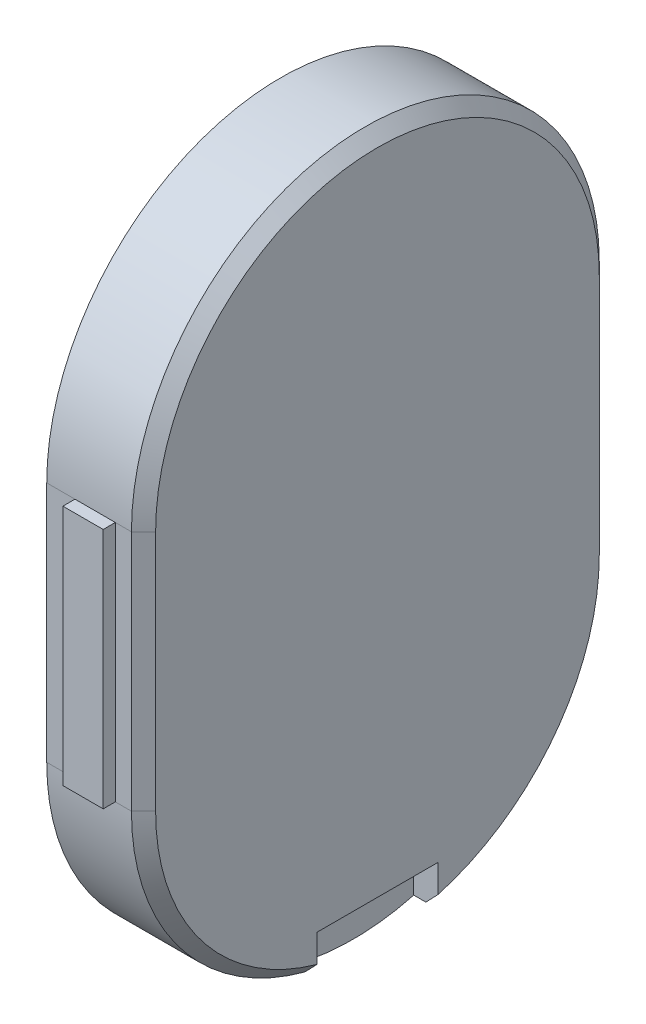
SolidWorks part; units mm, degrees
ref_plane "Front Plane" through (0, 0, 0) normal (0, 0, 1) x (1, 0, 0)
ref_plane "Top Plane" through (0, 0, 0) normal (0, 1, 0) x (1, 0, 0)
ref_plane "Right Plane" through (0, 0, 0) normal (1, 0, 0) x (0, 0, -1)
sketch "Sketch1" plane through (0, 0, 0) normal (1, 0, 0) x (0, 0, -1)
  line L0 (-94.1, 53) -> (-94.1, 59)
  line L1 (-82.5, 59) -> (-82.5, 53)
  arc A0 (-82.5, 53) -> (-88.3, 47.2) centre (-88.3, 53) cw
  arc A1 (-88.3, 47.2) -> (-94.1, 53) centre (-88.3, 53) cw
  arc A2 (-94.1, 59) -> (-88.3, 64.8) centre (-88.3, 59) cw
  arc A3 (-88.3, 64.8) -> (-82.5, 59) centre (-88.3, 59) cw
extrude "Boss-Extrude1" add sketch "Sketch1" along normal blind 2.4 from offset 35.6
chamfer "Chamfer1" distance 0.3 angle 45 4 edges at (38, 47.2, 88.3) (38, 56, 82.5) (38, 56, 94.1) (38, 64.8, 88.3)
sketch "Sketch2" plane through (0, 0, 0) normal (0, 0, 1) x (1, 0, 0)
  line L1 (36.3, 53) -> (37.3, 53)
  line L2 (36.3, 53) -> (36.3, 59)
  line L3 (36.3, 59) -> (37.3, 59)
  line L4 (37.3, 53) -> (37.3, 59)
extrude "Boss-Extrude2" add sketch "Sketch2" along normal blind 0.31 from offset 82.2
sketch "Sketch3" plane through (0, 0, 0) normal (0, 0, 1) x (1, 0, 0)
  line L1 (36.3, 53) -> (37.3, 53)
  line L2 (36.3, 53) -> (36.3, 59)
  line L3 (36.3, 59) -> (37.3, 59)
  line L4 (37.3, 53) -> (37.3, 59)
extrude "Boss-Extrude3" add sketch "Sketch3" along normal blind 0.31 from offset 94.09
sketch "Sketch4" plane through (0, 0, 0) normal (0, 0, 1) x (1, 0, 0)
  line L1 (37.4, 47.1) -> (38.1, 47.1)
  line L2 (37.4, 47.1) -> (37.4, 48.4)
  line L3 (37.4, 48.4) -> (38.1, 48.4)
  line L4 (38.1, 47.1) -> (38.1, 48.4)
extrude "Boss-Extrude4" add sketch "Sketch4" along normal blind 3 from offset 86.8 separate body
combine bodies "Combine1" operation type subtract main body 103 bodies to subtract 104
